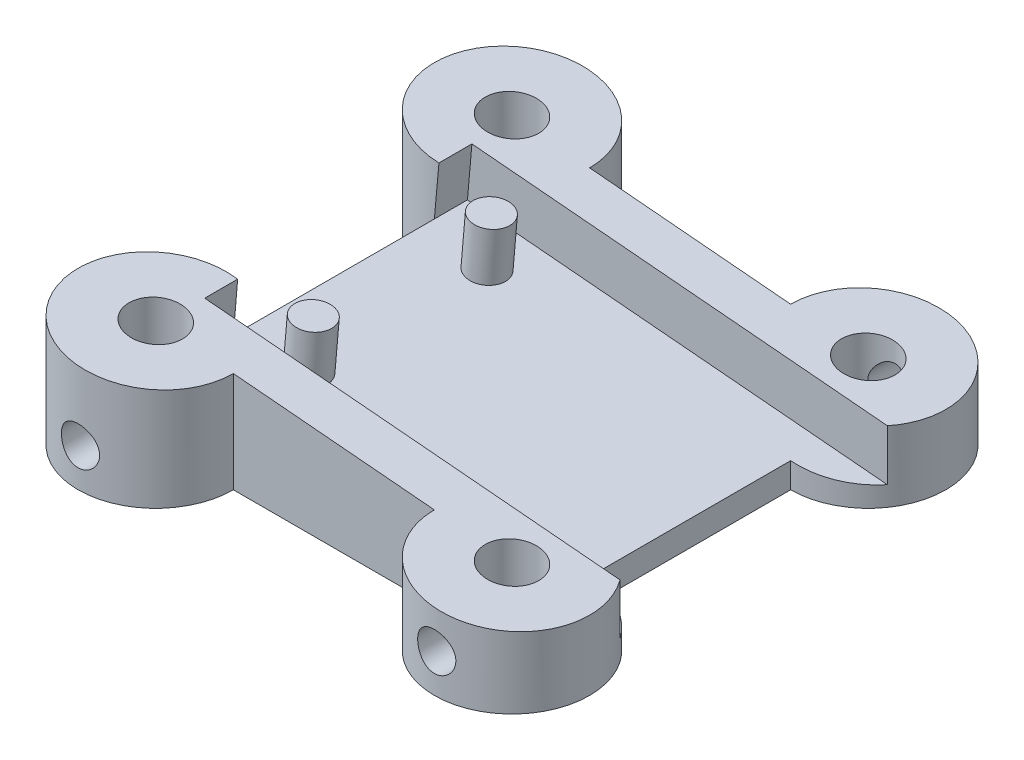
SolidWorks part; units mm, degrees
ref_plane "Front Plane" through (0, 0, 0) normal (0, 0, 1) x (1, 0, 0)
ref_plane "Top Plane" through (0, 0, 0) normal (0, 1, 0) x (1, 0, 0)
ref_plane "Right Plane" through (0, 0, 0) normal (1, 0, 0) x (0, 0, -1)
sketch "Sketch1" plane through (0, 0, 0) normal (0, 1, 0) x (1, 0, 0)
  line L0 (14, 28) -> (14, 0) construction
  line L1 (0, 0) -> (28, 0)
  line L2 (0, 0) -> (0, 28)
  line L3 (0, 28) -> (28, 28)
  line L4 (28, 0) -> (28, 28)
  line L5 (0, 14) -> (28, 14) construction
  point P9 (14, 14)
  dimension "D1" = 28
extrude "Boss-Extrude1" add sketch "Sketch1" along normal blind 8.4497
sketch "Sketch2" plane through (0, 0, 0) normal (0, 0, 1) x (1, 0, 0)
  line L0 (0, 8.4497) -> (28, 6)
  line L1 (0, 8.4497) -> (28, 8.4497) construction
  line L2 (28, 8.4497) -> (28, 0) construction
  line L3 (0, 8.4497) -> (28, 8.4497)
  line L4 (28, 8.4497) -> (28, 6)
  dimension "D2" = 6
  dimension "D3" = 5
extrude "Cut-Extrude1" cut sketch "Sketch2" against normal through all
sketch "Sketch3" plane through (0.7336, 8.3855, 0) normal (0.0872, 0.9962, 0) x (0.9962, -0.0872, 0)
  line L0 (-0.7364, 28) -> (-0.7364, 0) construction
  line L1 (-0.7364, 3.5) -> (49.2636, 3.5)
  line L2 (-0.7364, 3.5) -> (-0.7364, 24.5)
  line L3 (-0.7364, 24.5) -> (49.2636, 24.5)
  line L4 (49.2636, 3.5) -> (49.2636, 24.5)
  point P9 (-0.7364, 14)
  point P10 (-0.7364, 14)
  dimension "D1" = 21
  dimension "D2" = 50
extrude "Cut-Extrude2" cut sketch "Sketch3" against normal blind 4
ref_plane "Plane1" through (0, 8.4497, 0) normal (0, 1, 0) x (1, 0, 0)
sketch "Sketch11" plane through (0.385, 4.4007, 0) normal (0.0872, 0.9962, 0) x (0.9962, -0.0872, 0)
  line L0 (27.7205, 24.5) -> (-0.3865, 24.5) construction
  line L1 (27.7205, 24.5) -> (27.7205, 3.5) construction
  line L2 (-0.3865, 3.5) -> (27.7205, 3.5) construction
  line L3 (27.7205, 24.5) -> (-0.3865, 24.5) construction
  line L4 (27.7205, 24.5) -> (27.7205, 3.5) construction
  line L5 (-0.3865, 3.5) -> (27.7205, 3.5) construction
  line L6 (13.667, 3) -> (13.667, 50003) construction
  line L7 (24.633, 14) -> (-49975.367, 14) construction
  circle A2 centre (4.667, 21) radius 1.45
  circle A3 centre (4.667, 7) radius 1.45
  point P6 (13.667, 3.5)
  point P9 (27.7205, 14)
  dimension "D4" = 2.9
  dimension "D5" = 9
  dimension "D6" = 7
extrude "Boss-Extrude2" add sketch "Sketch11" along normal blind 4
sketch "Sketch12" plane through (0, 8.4497, 0) normal (0, 1, 0) x (1, 0, 0)
  line L0 (0, 3.5) -> (0, 24.5) construction
  line L1 (0, 3.5) -> (28, 3.5) construction
  line L2 (0, 3.5) -> (0, 24.5) construction
  line L3 (0, 3.5) -> (28, 3.5) construction
  line L4 (0, 14) -> (50000, 14) construction
  line L5 (14, 4) -> (14, 50004) construction
  circle A0 centre (14, 14) radius 7
  point P7 (0, 14)
  point P10 (14, 3.5)
  dimension "D1" = 14
sketch "Sketch13" plane through (0, 0, 0) normal (0, -1, 0) x (1, 0, 0)
  line L0 (0, 0) -> (28, 0) construction
  line L1 (28, 0) -> (28, -28) construction
  line L2 (28, -28) -> (0, -28) construction
  line L3 (0, -28) -> (0, 0) construction
  line L4 (0, 0) -> (28, 0) construction
  line L5 (28, 0) -> (28, -28) construction
  line L6 (28, -28) -> (0, -28) construction
  line L7 (0, -28) -> (0, 0) construction
  line L8 (0, -14) -> (28, -14) construction
  line L9 (14, -28) -> (14, 0) construction
  circle A0 centre (0, 0) radius 2.1
  circle A1 centre (28, 0) radius 2.1
  circle A2 centre (28, -28) radius 2.1
  circle A3 centre (0, -28) radius 2.1
  dimension "D1" = 4.2
  dimension "D2" = 2
  dimension "D3" = 2
extrude "Cut-Extrude5" cut sketch "Sketch13" against normal through all
sketch "Sketch14" plane through (0, 0, 0) normal (0, -1, 0) x (1, 0, 0)
  line L0 (28, -3.5) -> (28, -2.1) construction
  line L1 (2.1, -28) -> (25.9, -28) construction
  line L2 (0, -3.5) -> (0, -24.5) construction
  circle A0 centre (0, 0) radius 2.1 construction
  circle A1 centre (0, 0) radius 2.1 construction
  circle A2 centre (0, 0) radius 6.1
  circle A3 centre (0, 0) radius 2.1
  circle A4 centre (28, 0) radius 2.1
  circle A5 centre (28, 0) radius 6.1
  circle A6 centre (28, -28) radius 2.1
  circle A7 centre (28, -28) radius 6.1
  circle A8 centre (0, -28) radius 2.1
  circle A9 centre (0, -28) radius 6.1
  dimension "D1" = 4
  dimension "D4" = 4.2
  dimension "D2" = 2
  dimension "D3" = 2
extrude "Boss-Extrude3" add sketch "Sketch14" against normal up to surface (8.4497 mm away) up to face at (14, 7.2248, -25.9884)
sketch "Sketch15" plane through (0, 0, -28) normal (0, 0, -1) x (-1, 0, 0)
  line L0 (-21.9, 0) -> (-6.1, 0) construction
  line L1 (-21.9, 0) -> (-0.9, 0) construction
  line L4 (-14, 7.2248) -> (-14, 0) construction
  line L5 (-6.1, 7.916) -> (-21.9, 6.5337) construction
  circle A0 centre (-28, 3) radius 1.5
  circle A1 centre (0, 3) radius 1.5
  point P4 (-28, 0)
  dimension "D1" = 3
  dimension "D2" = 3
extrude "Cut-Extrude6" cut sketch "Sketch15" along normal through all
sketch "Sketch16" plane through (0, 0, 0) normal (0, 0, 1) x (1, 0, 0)
  circle A0 centre (0, 3) radius 1.5 construction
  circle A1 centre (28, 3) radius 1.5 construction
  circle A2 centre (0, 3) radius 1.5
  circle A3 centre (28, 3) radius 1.5
extrude "Cut-Extrude7" cut sketch "Sketch16" along normal through all
sketch "Sketch18" plane through (0.7336, 8.3855, 0) normal (0.0872, 0.9962, 0) x (0.9962, -0.0872, 0)
  line L5 (-0.7364, 3.5) -> (27.157, 3.5) construction
  line L8 (4.2786, 3.5) -> (22.3554, 3.5) construction
  line L9 (4.2786, 3.5) -> (22.3554, 3.5) construction
  line L22 (4.6286, 24.5) -> (-0.3865, 24.5)
  line L37 (7.3554, 3.5) -> (37.3554, 3.5)
  line L38 (7.3554, 3.5) -> (7.3554, 24.5)
  line L39 (7.3554, 24.5) -> (37.3554, 24.5)
  line L40 (37.3554, 3.5) -> (37.3554, 24.5)
  line L42 (-0.3865, 24.5) -> (-0.3865, 21.9)
  line L46 (-0.3865, 6.1) -> (-0.3865, 3.5)
  line L47 (-0.3865, 3.5) -> (4.6286, 3.5)
  line L49 (4.2786, 24.5) -> (22.3554, 24.5) construction
  ellipse E1 centre (-0.3865, 28) end of major axis (5.7368, 28) minor radius 6.1 (-0.3865, 21.9) -> (4.6286, 24.5) ccw construction
  ellipse E2 centre (-0.3865, 28) end of major axis (5.7368, 28) minor radius 6.1 (-0.3865, 21.9) -> (4.6286, 24.5) ccw
  ellipse E3 centre (-0.3865, 0) end of major axis (5.7368, 0) minor radius 6.1 (4.6286, 3.5) -> (-0.3865, 6.1) ccw construction
  ellipse E4 centre (-0.3865, 0) end of major axis (5.7368, 0) minor radius 6.1 (4.6286, 3.5) -> (-0.3865, 6.1) ccw
  point P7 (22.3554, 3.5)
  dimension "D1" = 30
extrude "Cut-Extrude8" cut sketch "Sketch18" against normal up to surface (4 mm away) up to face at (6.4787, 3.8676, -21)
equation "\"TrackLength\"= 150"
equation "\"MarbleWidth\"= 13"
equation "\"MarbleTrackWidth\"= \"MarbleWidth\" - 1"
equation "\"TrackWidth\"= \"MarbleTrackWidth\" + ( 2 * 4 )"
equation "\"MarbleTrackLength\"= \"TrackLength\" - ( 2 * 8 )"
equation "\"MountWidth\"= \"TrackWidth\" + 8"
equation "\"D1@Sketch1\"=\"MountWidth\""
equation "\"D1@Boss-Extrude1\"=\"RampHeight\""
equation "\"RampDepth\"=6"
equation "\"RampAngle\"= 5"
equation "\"RampHeight\"= ( \"MountWidth\" * tan ( \"RampAngle\" ) ) + \"RampDepth\""
equation "\"D1@Sketch3\"=\"TrackWidth\" + 1"
equation "\"MountWidth\"= \"TrackWidth\" + 10"
equation "\"MountLength\"=66.6651"
